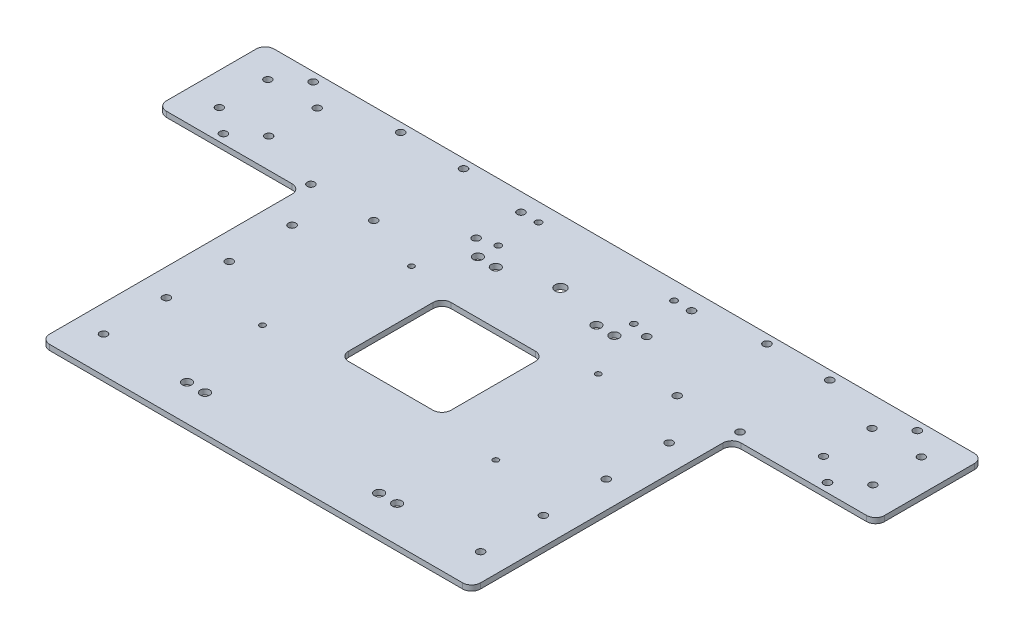
SolidWorks part; units mm, degrees
material "Thornel Mat VMA"
ref_plane "前视基准面" through (0, 0, 0) normal (0, 0, 1) x (1, 0, 0)
ref_plane "上视基准面" through (0, 0, 0) normal (0, 1, 0) x (1, 0, 0)
ref_plane "右视基准面" through (0, 0, 0) normal (1, 0, 0) x (0, 0, -1)
sketch "草图1" plane through (0, 0, 0) normal (0, 1, 0) x (1, 0, 0)
  line L0 (35.5759, -158.8718) -> (35.5759, 46.1282) construction
  line L1 (-164.4241, -13.8718) -> (235.5759, -13.8718)
  line L2 (-164.4241, -13.8718) -> (-164.4241, 46.1282)
  line L3 (-164.4241, 46.1282) -> (235.5759, 46.1282)
  line L4 (235.5759, -13.8718) -> (235.5759, 46.1282)
  line L5 (-11.9241, 36.1282) -> (83.0759, 36.1282) construction
  line L6 (-11.9241, 11.1282) -> (83.0759, 11.1282) construction
  line L7 (-84.4241, -158.8718) -> (155.5759, -158.8718)
  line L8 (-84.4241, -158.8718) -> (-84.4241, -13.8718)
  line L9 (-84.4241, -13.8718) -> (155.5759, -13.8718)
  line L10 (155.5759, -158.8718) -> (155.5759, -13.8718)
  line L11 (25.0759, 10.6282) -> (46.0759, 10.6282) construction
  line L12 (25.0759, 0.1282) -> (46.0759, 0.1282) construction
  line L13 (25.0759, 0.1282) -> (25.0759, 21.1282) construction
  line L14 (25.0759, 21.1282) -> (46.0759, 21.1282) construction
  line L15 (46.0759, 0.1282) -> (46.0759, 21.1282) construction
  line L16 (7.0759, -55.3718) -> (64.0759, -55.3718) construction
  line L17 (7.0759, -26.8718) -> (64.0759, -26.8718)
  line L18 (7.0759, -26.8718) -> (7.0759, -83.8718)
  line L19 (7.0759, -83.8718) -> (64.0759, -83.8718)
  line L20 (64.0759, -26.8718) -> (64.0759, -83.8718)
  line L21 (35.5759, 21.1282) -> (35.5759, 0.1282) construction
  circle A0 centre (-11.9241, 36.1282) radius 2.1
  circle A1 centre (-11.9241, 11.1282) radius 2.1
  circle A2 centre (83.0759, 11.1282) radius 2.1
  circle A3 centre (83.0759, 36.1282) radius 2.1
  circle A8 centre (35.5759, 10.6282) radius 3.05
  point P0 (0, 0)
  point P6 (0, -121.2547)
  point P16 (35.5759, 36.1282)
  point P19 (35.5759, 11.1282)
  point P23 (35.5759, 5.0732)
  point P30 (35.5759, -28.1434)
  point P35 (35.5759, -26.8718)
  dimension "D8" = 21
  dimension "D13" = 6.1
  dimension "D14" = 10.5
  dimension "D15" = 4.2
  dimension "D1" = 400
  dimension "D2" = 60
  dimension "D3" = 145
  dimension "D4" = 240
  dimension "D5" = 10
  dimension "D6" = 95
  dimension "D7" = 25
  dimension "D9" = 189.5
  dimension "D10" = 27
  dimension "D11" = 15
  dimension "D12" = 57
extrude "构型与裁判孔" add sketch "草图1" along normal blind 3 contours L1 L4 L3 L2 A3 L15 L12 L13 L14 A0 A1 A2 | L7 L10 L1 L8 region at (35.5759, 0, -16.1176) region at (35.5759, 0, 89.564)
sketch "草图2" plane through (0, 3, 0) normal (0, 1, 0) x (1, 0, 0)
  line L0 (-164.4241, 16.1282) -> (235.5759, 16.1282) construction
  line L1 (-164.4241, -13.8718) -> (-164.4241, 46.1282) construction
  line L2 (235.5759, -13.8718) -> (235.5759, 46.1282) construction
  line L3 (35.5759, 46.1282) -> (35.5759, -158.8718) construction
  line L4 (-164.4241, 46.1282) -> (235.5759, 46.1282) construction
  line L5 (-84.4241, -158.8718) -> (155.5759, -158.8718) construction
  line L6 (-146.4241, 2.6282) -> (-146.4241, 29.6282) construction
  line L7 (-118.9241, 2.6282) -> (-118.9241, 29.6282) construction
  line L8 (-146.4241, 29.6282) -> (-118.9241, 29.6282) construction
  line L9 (-48.9241, -8.8718) -> (-48.9241, 41.1282) construction
  line L10 (-132.6741, 29.6282) -> (-132.6741, 46.1282) construction
  line L11 (-132.6741, 41.1282) -> (-83.9241, 41.1282) construction
  circle A0 centre (-146.4241, 29.6282) radius 2.05
  circle A1 centre (-146.4241, 2.6282) radius 2.05
  circle A2 centre (-118.9241, 29.6282) radius 2.05
  circle A3 centre (-118.9241, 2.6282) radius 2.05
  circle A4 centre (-48.9241, 41.1282) radius 2.1
  circle A5 centre (-83.9241, 41.1282) radius 2.1
  circle A6 centre (-48.9241, -8.8718) radius 2.1
  circle A7 centre (-83.9241, -8.8718) radius 2.1
  circle A8 centre (-132.6741, 41.1282) radius 2.1
  circle A9 centre (-132.6741, -8.8718) radius 2.1
  circle A10 centre (203.8259, -8.8718) radius 2.1
  circle A11 centre (203.8259, 41.1282) radius 2.1
  circle A12 centre (155.0759, -8.8718) radius 2.1
  circle A13 centre (120.0759, -8.8718) radius 2.1
  circle A14 centre (155.0759, 41.1282) radius 2.1
  circle A15 centre (120.0759, 41.1282) radius 2.1
  circle A16 centre (190.0759, 2.6282) radius 2.05
  circle A17 centre (190.0759, 29.6282) radius 2.05
  circle A18 centre (217.5759, 2.6282) radius 2.05
  circle A19 centre (217.5759, 29.6282) radius 2.05
  point P15 (-146.4241, 16.1282)
  point P20 (-118.9241, 16.1282)
  point P25 (-48.9241, 16.1282)
  dimension "D2" = 4.1
  dimension "D4" = 5
  dimension "D5" = 4.2
  dimension "D7" = 2
  dimension "D8" = 18
  dimension "D1" = 27
  dimension "D3" = 45.5
  dimension "D6" = 70
extrude "切除-拉伸1" cut sketch "草图2" against normal through all
fillet "圆角1" radius 5 12 edges at (155.5759, 1.5, 13.8718) (-84.4241, 1.5, 13.8718) (235.5759, 1.5, -46.1282) (235.5759, 1.5, 13.8718) (155.5759, 1.5, 158.8718) (-84.4241, 1.5, 158.8718) (-164.4241, 1.5, -46.1282) (-164.4241, 1.5, 13.8718) (7.0759, 1.5, 83.8718) (64.0759, 1.5, 83.8718) (64.0759, 1.5, 26.8718) (7.0759, 1.5, 26.8718)
sketch "草图3" plane through (0, 3, 0) normal (0, 1, 0) x (1, 0, 0)
  line L0 (-89.4241, -13.8718) -> (160.5759, -13.8718) construction
  line L1 (-69.4241, -13.8718) -> (-69.4241, -158.8718) construction
  line L2 (-79.4241, -158.8718) -> (150.5759, -158.8718) construction
  line L3 (35.5759, 46.1282) -> (35.5759, -158.8718) construction
  line L4 (-159.4241, 46.1282) -> (230.5759, 46.1282) construction
  line L5 (-84.4241, -153.8718) -> (-84.4241, -18.8718) construction
  line L6 (7.0759, -55.3718) -> (64.0759, -55.3718) construction
  line L7 (190.0759, 2.6282) -> (-118.9241, 2.6282) construction
  line L8 (-16.4241, -20.3718) -> (-29.4241, -20.3718) construction
  line L9 (-48.9617, -13.8718) -> (-48.9617, -158.8718) construction
  line L10 (-79.4241, -158.8718) -> (150.5759, -158.8718) construction
  line L11 (-84.4241, -153.8718) -> (-84.4241, -18.8718) construction
  line L12 (-16.4241, -20.3718) -> (-16.4241, -90.3718) construction
  line L13 (-16.4241, -90.3718) -> (-29.4241, -90.3718) construction
  line L14 (-29.4241, -20.3718) -> (-29.4241, -90.3718) construction
  line L15 (-22.9241, -90.3718) -> (-22.9241, -20.3718) construction
  line L16 (-16.4241, -55.3718) -> (-29.4241, -55.3718) construction
  line L17 (7.0759, -31.8718) -> (7.0759, -78.8718) construction
  line L18 (-69.4241, -138.8718) -> (140.5759, -138.8718) construction
  circle A0 centre (-69.4241, -33.8718) radius 2.1
  circle A1 centre (-69.4241, -68.8718) radius 2.1
  circle A2 centre (-69.4241, -103.8718) radius 2.1
  circle A3 centre (-69.4241, -138.8718) radius 2.1
  circle A4 centre (140.5759, -138.8718) radius 2.1
  circle A5 centre (140.5759, -103.8718) radius 2.1
  circle A6 centre (140.5759, -68.8718) radius 2.1
  circle A7 centre (140.5759, -33.8718) radius 2.1
  circle A8 centre (-16.4241, -20.3718) radius 1.55
  circle A9 centre (-29.4241, -90.3718) radius 1.55
  circle A10 centre (100.5759, -90.3718) radius 1.55
  circle A11 centre (87.5759, -20.3718) radius 1.55
  circle A12 centre (-2.4241, 2.6282) radius 2.6
  circle A13 centre (7.5759, 2.6282) radius 2.6
  circle A14 centre (63.5759, 2.6282) radius 2.6
  circle A15 centre (73.5759, 2.6282) radius 2.6
  circle A16 centre (-22.9241, -138.8718) radius 2.6
  circle A17 centre (-12.9241, -138.8718) radius 2.6
  circle A18 centre (84.0759, -138.8718) radius 2.6
  circle A19 centre (94.0759, -138.8718) radius 2.6
  point P44 (7.0759, -55.3718)
  point P495 (-22.9241, -55.3718)
  dimension "D1" = 20
  dimension "D2" = 35
  dimension "D3" = 35
  dimension "D4" = 35
  dimension "D7" = 3.1
  dimension "D10" = 5.2
  dimension "D11" = 10
  dimension "D12" = 28
  dimension "D14" = 10
  dimension "D5" = 15
  dimension "D6" = 35.4624
  dimension "D8" = 13
  dimension "D9" = 70
  dimension "D13" = 20
  dimension "D15" = 40
extrude "切除-拉伸2" cut sketch "草图3" against normal through all
sketch "草图4" plane through (0, 3, 0) normal (0, 1, 0) x (1, 0, 0)
  line L0 (35.5759, -26.8718) -> (35.5759, 119.4643) construction
  line L1 (12.0759, -26.8718) -> (59.0759, -26.8718) construction
  line L2 (-2.1741, 36.1282) -> (73.3259, 36.1282)
  line L3 (-159.4241, 46.1282) -> (230.5759, 46.1282) construction
  line L4 (-2.1741, 36.1282) -> (-2.1741, 13.7282) construction
  circle A0 centre (-2.1741, 36.1282) radius 1.75
  circle A1 centre (73.3259, 36.1282) radius 1.75
  circle A2 centre (-2.1741, 13.7282) radius 1.75
  circle A3 centre (73.3259, 13.7282) radius 1.75
  point P7 (35.5759, 36.1282)
  dimension "D3" = 3.5
  dimension "D4" = 3.5
  dimension "D6" = 3.5
  dimension "D1" = 75.5
  dimension "D2" = 10
  dimension "D5" = 22.4
extrude "切除-拉伸3" cut sketch "草图4" against normal blind 10 contours A0 | A2 | A1 | A3
